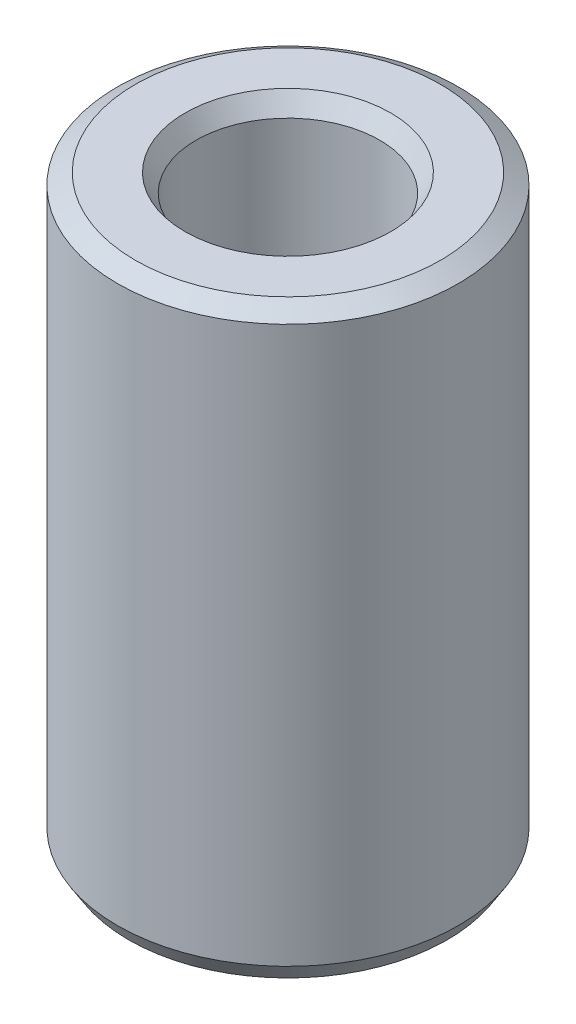
SolidWorks part; units mm, degrees
ref_plane "Front Plane" through (0, 0, 0) normal (0, 0, 1) x (1, 0, 0)
ref_plane "Top Plane" through (0, 0, 0) normal (0, 1, 0) x (1, 0, 0)
ref_plane "Right Plane" through (0, 0, 0) normal (1, 0, 0) x (0, 0, -1)
sketch "Sketch1" plane through (0, 0, 0) normal (0, 1, 0) x (1, 0, 0)
  circle A0 centre (0, 0) radius 52.5
  dimension "SLEEVE_OD" = 105
extrude "Boss-Extrude1" add sketch "Sketch1" along normal blind 180.2015
sketch "Sketch2" plane through (0, 0, 0) normal (0, 1, 0) x (1, 0, 0)
  circle A0 centre (0, 0) radius 28.2542
  dimension "BORE_D" = 56.5084
extrude "Cut-Extrude1" cut sketch "Sketch2" along normal through all
chamfer "Chamfer1" distance 3.4298 angle 58.173 4 edges at (0, 180.2015, 28.2542) (0, 0, 28.2542) (0, 0, 52.5) (0, 180.2015, 52.5) first distance on face at (0, 180.2015, 28.2542) first distance on face at (0, 0, 28.2542) first distance on face at (0, 180.2015, 52.5)
